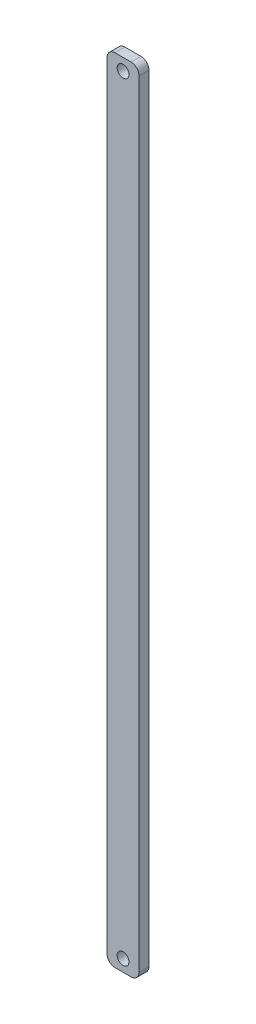
SolidWorks part; units mm, degrees
ref_plane "Front Plane" through (0, 0, 0) normal (0, 0, 1) x (1, 0, 0)
ref_plane "Top Plane" through (0, 0, 0) normal (0, 1, 0) x (1, 0, 0)
ref_plane "Right Plane" through (0, 0, 0) normal (1, 0, 0) x (0, 0, -1)
sketch "Sketch1" plane through (0, 0, 0) normal (0, 1, 0) x (1, 0, 0)
  line L1 (-4.03, -1.25) -> (4.03, -1.25)
  line L2 (-4.03, -1.25) -> (-4.03, 1.25)
  line L3 (-4.03, 1.25) -> (4.03, 1.25)
  line L4 (4.03, -1.25) -> (4.03, 1.25)
  line L5 (-4.03, -1.25) -> (4.03, 1.25) construction
  line L6 (-4.03, 1.25) -> (4.03, -1.25) construction
  point P0 (0, 0)
  dimension "D1" = 8.06
  dimension "D2" = 2.5
extrude "Boss-Extrude1" add sketch "Sketch1" along normal blind 200
sketch "Sketch2" plane through (0, 0, 1.25) normal (0, 0, 1) x (1, 0, 0)
  line L0 (-4.03, 200) -> (-4.03, 0) construction
  line L1 (4.03, 100) -> (-4.03, 100) construction
  line L2 (4.03, 200) -> (4.03, 0) construction
  circle A0 centre (0, 3) radius 1.5
  circle A1 centre (0, 197) radius 1.5
  dimension "D2" = 3
  dimension "D1" = 3
  dimension "D3" = 4.03
extrude "Cut-Extrude1" cut sketch "Sketch2" against normal up to surface (2.5 mm away) up to face at (0, 100, -1.25)
fillet "Fillet1" radius 2 4 edges at (-4.03, 0, 0) (4.03, 0, 0) (-4.03, 200, 0) (4.03, 200, 0)
